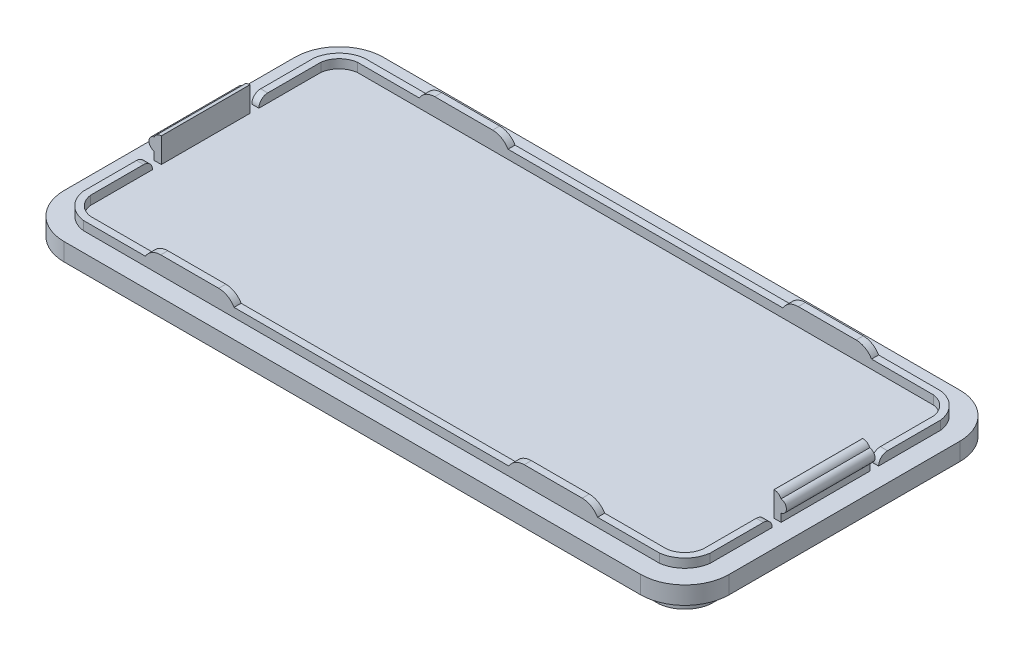
SolidWorks part; units mm, degrees
ref_plane "前视基准面" through (0, 0, 0) normal (0, 0, 1) x (1, 0, 0)
ref_plane "上视基准面" through (0, 0, 0) normal (0, 1, 0) x (1, 0, 0)
ref_plane "右视基准面" through (0, 0, 0) normal (1, 0, 0) x (0, 0, -1)
sketch "zero" plane through (0, 0, 0) normal (0, 1, 0) x (1, 0, 0)
  line L1 (-29.5, 15) -> (29.5, 15)
  line L2 (-32.5, 12) -> (-32.5, -12)
  line L3 (-29.5, -15) -> (29.5, -15)
  line L4 (32.5, 12) -> (32.5, -12)
  line L5 (-32.5, 15) -> (32.5, -15) construction
  line L6 (-32.5, -15) -> (32.5, 15) construction
  line L7 (-25.7, -15) -> (-14.5, -15)
  line L8 (-25.7, -15) -> (-25.7, -9.6569)
  line L9 (-25.7, -9.6569) -> (-14.5, -9.6569)
  line L10 (-14.5, -15) -> (-14.5, -9.6569)
  line L11 (5.2, -15) -> (12.7, -15)
  line L12 (5.2, -15) -> (5.2, -11)
  line L13 (5.2, -11) -> (12.7, -11)
  line L14 (12.7, -15) -> (12.7, -11)
  line L15 (17.8, -15) -> (25.3, -15)
  line L16 (17.8, -15) -> (17.8, -11)
  line L17 (17.8, -11) -> (25.3, -11)
  line L18 (25.3, -15) -> (25.3, -11)
  line L19 (-32.5, 7.7) -> (-19.5, 7.7)
  line L20 (-32.5, 7.7) -> (-32.5, -4.3)
  line L21 (-32.5, -4.3) -> (-19.5, -4.3)
  line L22 (-19.5, 7.7) -> (-19.5, -4.3)
  line L23 (-25.5, 14) -> (25.5, 14)
  line L24 (-25.5, 14) -> (-25.5, 8.8)
  line L25 (-25.5, 8.8) -> (25.5, 8.8)
  line L26 (25.5, 14) -> (25.5, 8.8)
  line L27 (-19.5, 7.2329) -> (-35.5, 7.2329)
  line L28 (-19.5, 7.2329) -> (-19.5, -3.7671)
  line L29 (-19.5, -3.7671) -> (-35.5, -3.7671)
  line L30 (-35.5, 7.2329) -> (-35.5, -3.7671)
  arc A0 (29.5, -15) -> (32.5, -12) centre (29.5, -12) ccw
  arc A1 (29.5, 15) -> (32.5, 12) centre (29.5, 12) cw
  arc A2 (-32.5, -12) -> (-29.5, -15) centre (-29.5, -12) ccw
  arc A3 (-29.5, 15) -> (-32.5, 12) centre (-29.5, 12) ccw
  circle A4 centre (-29, 11.4) radius 3
  circle A5 centre (-29, -11.5) radius 3
  circle A6 centre (29, 11.4) radius 3
  circle A7 centre (29, -11.5) radius 3
  circle A8 centre (-29, 11.4) radius 1.375
  circle A9 centre (-29, -11.5) radius 1.375
  circle A10 centre (29, -11.5) radius 1.375
  circle A11 centre (29, 11.4) radius 1.375
  point P0 (0, 0)
  dimension "D3" = 3
  dimension "D4" = 6
  dimension "D9" = 2.75
  dimension "D1" = 65
  dimension "D2" = 30
  dimension "D5" = 3.6
  dimension "D6" = 3.5
  dimension "D7" = 3.5
  dimension "D8" = 3.5
  dimension "D10" = 12
  dimension "D11" = 7.3
  dimension "D12" = 13
  dimension "D13" = 11.2
  dimension "D14" = 6.8
  dimension "D15" = 19.7
  dimension "D16" = 7.5
  dimension "D17" = 7.5
  dimension "D18" = 5.1
  dimension "D19" = 4
  dimension "D20" = 5.2
  dimension "D21" = 7
  dimension "D22" = 7
  dimension "D23" = 1
  dimension "D24" = 11
  dimension "D25" = 16
sketch "sugar" plane through (0, 0, 0) normal (0, 1, 0) x (1, 0, 0)
  line L1 (-29.5, 15) -> (29.5, 15)
  line L2 (-32.5, 12) -> (-32.5, -12)
  line L3 (-29.5, -15) -> (29.5, -15)
  line L4 (32.5, 12) -> (32.5, -12)
  line L5 (-32.5, 15) -> (32.5, -15) construction
  line L6 (-32.5, -15) -> (32.5, 15) construction
  line L7 (23.5, -11.5) -> (19.5, -11.5)
  line L8 (23.5, -11.5) -> (23.5, -13.9082)
  line L9 (23.5, -13.9082) -> (19.5, -13.9082)
  line L10 (19.5, -11.5) -> (19.5, -13.9082)
  line L11 (16, -11.0071) -> (8.5, -11.0071)
  line L12 (16, -11.0071) -> (16, -15)
  line L13 (16, -15) -> (8.5, -15)
  line L14 (8.5, -11.0071) -> (8.5, -15)
  line L15 (20.5, -13.9082) -> (22.5, -13.9082)
  line L16 (20.5, -13.9082) -> (20.5, -14.8173)
  line L17 (20.5, -14.8173) -> (22.5, -14.8173)
  line L18 (22.5, -13.9082) -> (22.5, -14.8173)
  arc A0 (29.5, 15) -> (32.5, 12) centre (29.5, 12) cw
  arc A1 (29.5, -15) -> (32.5, -12) centre (29.5, -12) ccw
  arc A2 (-32.5, -12) -> (-29.5, -15) centre (-29.5, -12) ccw
  arc A3 (-29.5, 15) -> (-32.5, 12) centre (-29.5, 12) ccw
  circle A4 centre (-29, 11.4) radius 3
  circle A5 centre (-29, 11.4) radius 1.375
  circle A6 centre (-29, -11.5) radius 3
  circle A7 centre (-29, -11.5) radius 1.375
  circle A8 centre (29, 11.4) radius 3
  circle A9 centre (29, 11.4) radius 1.375
  circle A10 centre (29, -11.5) radius 3
  circle A11 centre (29, -11.5) radius 1.375
  dimension "D3" = 3
  dimension "D1" = 65
  dimension "D2" = 30
  dimension "D4" = 9
  dimension "D5" = 4
  dimension "D6" = 3.5
  dimension "D7" = 7.5
  dimension "D8" = 2
  dimension "D9" = 1
sketch "case" plane through (0, 0, 0) normal (0, 1, 0) x (1, 0, 0)
  line L1 (-34.0422, 18) -> (30.9578, 18)
  line L2 (-39.0422, 13) -> (-39.0422, -13)
  line L3 (-34.0422, -18) -> (30.9578, -18)
  line L4 (35.9578, 13) -> (35.9578, -13)
  line L5 (-39.0422, 18) -> (35.9578, -18) construction
  line L6 (-39.0422, -18) -> (35.9578, 18) construction
  arc A0 (-39.0422, -13) -> (-34.0422, -18) centre (-34.0422, -13) ccw
  arc A1 (30.9578, -18) -> (35.9578, -13) centre (30.9578, -13) ccw
  arc A2 (30.9578, 18) -> (35.9578, 13) centre (30.9578, 13) cw
  arc A3 (-34.0422, 18) -> (-39.0422, 13) centre (-34.0422, 13) ccw
  point P0 (-1.5422, 0)
  point P3 (-1.5422, 0)
  dimension "D3" = 5
  dimension "D1" = 75
  dimension "D2" = 36
extrude "凸台-拉伸2" add sketch "case" along normal blind 2
sketch "草图2" plane through (0, 0, 0) normal (0, 1, 0) x (1, 0, 0)
  line L0 (-39.0422, 13) -> (-39.0422, -13) construction
  line L1 (30.9578, 18) -> (-34.0422, 18) construction
  line L4 (-34.0422, -15.05) -> (30.9578, -15.05)
  line L5 (33.0078, -13) -> (33.0078, 13)
  line L6 (30.9578, 15.05) -> (-34.0422, 15.05)
  line L7 (-36.0922, 13) -> (-36.0922, -13)
  line L12 (33.8078, -13) -> (33.8078, 13)
  line L13 (30.9578, 15.85) -> (-34.0422, 15.85)
  line L14 (-36.8922, 13) -> (-36.8922, -13)
  line L15 (-34.0422, -15.85) -> (30.9578, -15.85)
  arc A4 (30.9578, -15.05) -> (33.0078, -13) centre (30.6303, -12.6725) ccw
  arc A5 (33.0078, 13) -> (30.9578, 15.05) centre (30.6303, 12.6725) ccw
  arc A6 (-34.0422, 15.05) -> (-36.0922, 13) centre (-33.7147, 12.6725) ccw
  arc A7 (-36.0922, -13) -> (-34.0422, -15.05) centre (-33.7147, -12.6725) ccw
  arc A12 (30.9578, -15.85) -> (33.8078, -13) centre (30.535, -12.5772) ccw
  arc A13 (33.8078, 13) -> (30.9578, 15.85) centre (30.535, 12.5772) ccw
  arc A14 (-34.0422, 15.85) -> (-36.8922, 13) centre (-33.6194, 12.5772) ccw
  arc A15 (-36.8922, -13) -> (-34.0422, -15.85) centre (-33.6194, -12.5772) ccw
ref_plane "基准面1" through (0, 2, 0) normal (0, 1, 0) x (1, 0, 0)
sketch "草图3" plane through (0, 2, 0) normal (0, 1, 0) x (1, 0, 0)
  line L4 (-34.0422, -15.05) -> (30.9578, -15.05)
  line L5 (33.0078, -13) -> (33.0078, 13)
  line L6 (30.9578, 15.05) -> (-34.0422, 15.05)
  line L7 (-36.0922, 13) -> (-36.0922, -13)
  line L8 (-34.0422, -15.05) -> (30.9578, -15.05)
  line L9 (33.0078, -13) -> (33.0078, 13)
  line L10 (30.9578, 15.05) -> (-34.0422, 15.05)
  line L11 (-36.0922, 13) -> (-36.0922, -13)
  line L12 (-36.8922, 13) -> (-36.8922, -13)
  line L13 (-34.0422, -15.85) -> (30.9578, -15.85)
  line L14 (33.8078, -13) -> (33.8078, 13)
  line L15 (30.9578, 15.85) -> (-34.0422, 15.85)
  line L16 (-36.8922, 13) -> (-36.8922, -13)
  line L17 (-34.0422, -15.85) -> (30.9578, -15.85)
  line L18 (33.8078, -13) -> (33.8078, 13)
  line L19 (30.9578, 15.85) -> (-34.0422, 15.85)
  arc A4 (30.9578, -15.05) -> (33.0078, -13) centre (30.6303, -12.6725) ccw
  arc A5 (33.0078, 13) -> (30.9578, 15.05) centre (30.6303, 12.6725) ccw
  arc A6 (-34.0422, 15.05) -> (-36.0922, 13) centre (-33.7147, 12.6725) ccw
  arc A7 (-36.0922, -13) -> (-34.0422, -15.05) centre (-33.7147, -12.6725) ccw
  arc A8 (30.9578, -15.05) -> (33.0078, -13) centre (30.6303, -12.6725) ccw
  arc A9 (33.0078, 13) -> (30.9578, 15.05) centre (30.6303, 12.6725) ccw
  arc A10 (-34.0422, 15.05) -> (-36.0922, 13) centre (-33.7147, 12.6725) ccw
  arc A11 (-36.0922, -13) -> (-34.0422, -15.05) centre (-33.7147, -12.6725) ccw
  arc A12 (-36.8922, -13) -> (-34.0422, -15.85) centre (-33.6194, -12.5772) ccw
  arc A13 (30.9578, -15.85) -> (33.8078, -13) centre (30.535, -12.5772) ccw
  arc A14 (33.8078, 13) -> (30.9578, 15.85) centre (30.535, 12.5772) ccw
  arc A15 (-34.0422, 15.85) -> (-36.8922, 13) centre (-33.6194, 12.5772) ccw
  arc A16 (-36.8922, -13) -> (-34.0422, -15.85) centre (-33.6194, -12.5772) ccw
  arc A17 (30.9578, -15.85) -> (33.8078, -13) centre (30.535, -12.5772) ccw
  arc A18 (33.8078, 13) -> (30.9578, 15.85) centre (30.535, 12.5772) ccw
  arc A19 (-34.0422, 15.85) -> (-36.8922, 13) centre (-33.6194, 12.5772) ccw
  dimension "D1" = 0
  dimension "D2" = 0
extrude "凸台-拉伸4" add sketch "草图3" along normal blind 1
ref_plane "基准面3" through (33.8078, 0, 0) normal (1, 0, 0) x (0, 0, -1)
sketch "草图7" plane through (0, 2, 0) normal (0, 1, 0) x (1, 0, 0)
  line L0 (-36.8922, 13) -> (-36.8922, -13) construction
  line L1 (-36.8922, 5) -> (-36.0922, 5)
  line L2 (-36.8922, 5) -> (-36.8922, -5)
  line L3 (-36.8922, -5) -> (-36.0922, -5)
  line L4 (-36.0922, 5) -> (-36.0922, -5)
  line L5 (-36.0922, 13) -> (-36.0922, -13) construction
  point P10 (-36.0922, 0)
  dimension "D1" = 5
  dimension "D2" = 10
extrude "凸台-拉伸8" add sketch "草图7" along normal blind 2.8
ref_plane "基准面5" through (0, 0, 5) normal (0, 0, 1) x (1, 0, 0)
sketch "草图8" plane through (0, 0, 5) normal (0, 0, 1) x (1, 0, 0)
  line L0 (-34.0422, 2) -> (-39.0422, 2) construction
  line L1 (-36.8922, 4.8) -> (-36.8922, 3) construction
  circle A0 centre (-36.7922, 3.6) radius 0.7
  dimension "D1" = 1.4
  dimension "D2" = 1.6
  dimension "D3" = 0.1
extrude "凸台-拉伸9" add sketch "草图8" against normal blind 10
fillet "圆角1" radius 0.85 1 edges at (-36.8922, 4.8, 0)
ref_plane "基准面7" through (-36.8922, 0, 0) normal (-1, 0, 0) x (0, 0, 1)
sketch "草图11" plane through (-36.8922, 0, 0) normal (-1, 0, 0) x (0, 0, 1)
  line L0 (-13, 2) -> (13, 2) construction
  line L1 (5, 3) -> (6, 3)
  line L2 (5, 3) -> (5, 2)
  line L3 (5, 2) -> (6, 2)
  line L4 (6, 3) -> (6, 2)
  line L6 (-5, 3) -> (-6, 3)
  line L7 (-5, 3) -> (-5, 2)
  line L8 (-5, 2) -> (-6, 2)
  line L9 (-6, 3) -> (-6, 2)
  dimension "D1" = 1
  dimension "D2" = 1
extrude "切除-拉伸1" cut sketch "草图11" against normal blind 1.2
fillet "圆角2" radius 1 2 edges at (-36.4922, 3, 6) (-36.4922, 3, -6)
ref_plane "基准面8" through (0, 0, 0) normal (0, -1, 0) x (-1, 0, 0)
sketch "草图13" plane through (0, 3, 0) normal (0, 1, 0) x (1, 0, 0)
  line L0 (33.0078, -13) -> (33.0078, 13) construction
  line L1 (33.0078, 5) -> (33.8078, 5)
  line L2 (33.0078, 5) -> (33.0078, -5)
  line L3 (33.0078, -5) -> (33.8078, -5)
  line L4 (33.8078, 5) -> (33.8078, -5)
  line L5 (33.8078, -13) -> (33.8078, 13) construction
  line L7 (35.9578, -13) -> (35.9578, 13) construction
  point P12 (35.9578, 0)
  point P13 (33.8078, 0)
  dimension "D1" = 10
extrude "凸台-拉伸10" add sketch "草图13" along normal blind 1.8
sketch "草图14" plane through (0, 0, 5) normal (0, 0, 1) x (1, 0, 0)
  line L0 (33.8078, 2) -> (30.9578, 2) construction
  line L1 (33.8078, 4.8) -> (33.8078, 3) construction
  circle A0 centre (33.7078, 3.6) radius 0.7
  dimension "D2" = 1.4
  dimension "D1" = 1.6
  dimension "D3" = 0.1
extrude "凸台-拉伸11" add sketch "草图14" against normal blind 10
fillet "圆角3" radius 0.85 1 edges at (33.8078, 4.8, 0)
sketch "草图15" plane through (0, 3, 0) normal (0, 1, 0) x (1, 0, 0)
  line L0 (33.8078, 5) -> (33.8078, 13) construction
  line L1 (33.0078, 5) -> (33.8078, 5)
  line L2 (33.0078, 5) -> (33.0078, 6)
  line L3 (33.0078, 6) -> (33.8078, 6)
  line L4 (33.8078, 5) -> (33.8078, 6)
  line L5 (33.8078, -13) -> (33.8078, -5) construction
  line L6 (33.0078, -5) -> (33.8078, -5)
  line L7 (33.0078, -5) -> (33.0078, -6)
  line L8 (33.0078, -6) -> (33.8078, -6)
  line L9 (33.8078, -5) -> (33.8078, -6)
  dimension "D1" = 1
  dimension "D2" = 1
extrude "切除-拉伸3" cut sketch "草图15" against normal blind 1
fillet "圆角4" radius 1 2 edges at (33.4078, 3, 6) (33.4078, 3, -6)
sketch "草图16" plane through (0, 2, 0) normal (0, 1, 0) x (1, 0, 0)
  line L4 (-34.0422, -15.05) -> (30.9578, -15.05)
  line L5 (33.0078, -13) -> (33.0078, 13)
  line L6 (30.9578, 15.05) -> (-34.0422, 15.05)
  line L7 (-36.0922, 13) -> (-36.0922, -13)
  line L8 (-34.0422, -15.05) -> (30.9578, -15.05)
  line L9 (33.0078, -13) -> (33.0078, 13)
  line L10 (30.9578, 15.05) -> (-34.0422, 15.05)
  line L11 (-36.0922, 13) -> (-36.0922, -13)
  arc A4 (30.9578, -15.05) -> (33.0078, -13) centre (30.6303, -12.6725) ccw
  arc A5 (33.0078, 13) -> (30.9578, 15.05) centre (30.6303, 12.6725) ccw
  arc A6 (-34.0422, 15.05) -> (-36.0922, 13) centre (-33.7147, 12.6725) ccw
  arc A7 (-36.0922, -13) -> (-34.0422, -15.05) centre (-33.7147, -12.6725) ccw
  arc A8 (30.9578, -15.05) -> (33.0078, -13) centre (30.6303, -12.6725) ccw
  arc A9 (33.0078, 13) -> (30.9578, 15.05) centre (30.6303, 12.6725) ccw
  arc A10 (-34.0422, 15.05) -> (-36.0922, 13) centre (-33.7147, 12.6725) ccw
  arc A11 (-36.0922, -13) -> (-34.0422, -15.05) centre (-33.7147, -12.6725) ccw
  dimension "D1" = 0
extrude "凸台-拉伸12" add sketch "草图2" against normal blind 2
sketch "草图18" plane through (0, 0, 0) normal (0, -1, 0) x (1, 0, 0)
  line L2 (-34.0422, 18) -> (30.9578, 18) construction
  line L3 (-39.0422, -13) -> (-39.0422, 13) construction
  circle A0 centre (-37.3172, 15.9) radius 3.225
  circle A1 centre (-37.3172, 15.9) radius 2.225
  circle A2 centre (-29.3672, 15.9) radius 2.225
  circle A3 centre (-29.3672, 15.9) radius 3.225
  circle A4 centre (-21.4172, 15.9) radius 2.225
  circle A5 centre (-21.4172, 15.9) radius 3.225
  circle A6 centre (-13.4672, 15.9) radius 2.225
  circle A7 centre (-13.4672, 15.9) radius 3.225
  circle A8 centre (-5.5172, 15.9) radius 2.225
  circle A9 centre (-5.5172, 15.9) radius 3.225
  circle A10 centre (2.4328, 15.9) radius 2.225
  circle A11 centre (2.4328, 15.9) radius 3.225
  circle A12 centre (10.3828, 15.9) radius 2.225
  circle A13 centre (10.3828, 15.9) radius 3.225
  circle A14 centre (18.3328, 15.9) radius 2.225
  circle A15 centre (18.3328, 15.9) radius 3.225
  circle A16 centre (26.2828, 15.9) radius 2.225
  circle A17 centre (26.2828, 15.9) radius 3.225
  circle A18 centre (34.2328, 15.9) radius 2.225
  circle A19 centre (34.2328, 15.9) radius 3.225
  circle A20 centre (-29.3672, 7.95) radius 2.225
  circle A21 centre (-29.3672, 7.95) radius 3.225
  circle A22 centre (-21.4172, 7.95) radius 2.225
  circle A23 centre (-21.4172, 7.95) radius 3.225
  circle A24 centre (-13.4672, 7.95) radius 2.225
  circle A25 centre (-13.4672, 7.95) radius 3.225
  circle A26 centre (-5.5172, 7.95) radius 2.225
  circle A27 centre (-5.5172, 7.95) radius 3.225
  circle A28 centre (2.4328, 7.95) radius 2.225
  circle A29 centre (2.4328, 7.95) radius 3.225
  circle A30 centre (10.3828, 7.95) radius 2.225
  circle A31 centre (10.3828, 7.95) radius 3.225
  circle A32 centre (18.3328, 7.95) radius 2.225
  circle A33 centre (18.3328, 7.95) radius 3.225
  circle A34 centre (26.2828, 7.95) radius 2.225
  circle A35 centre (26.2828, 7.95) radius 3.225
  circle A36 centre (34.2328, 7.95) radius 2.225
  circle A37 centre (34.2328, 7.95) radius 3.225
  circle A38 centre (-29.3672, 0) radius 2.225
  circle A39 centre (-29.3672, 0) radius 3.225
  circle A40 centre (-21.4172, 0) radius 2.225
  circle A41 centre (-21.4172, 0) radius 3.225
  circle A42 centre (-13.4672, 0) radius 2.225
  circle A43 centre (-13.4672, 0) radius 3.225
  circle A44 centre (-5.5172, 0) radius 2.225
  circle A45 centre (-5.5172, 0) radius 3.225
  circle A46 centre (2.4328, 0) radius 2.225
  circle A47 centre (2.4328, 0) radius 3.225
  circle A48 centre (10.3828, 0) radius 2.225
  circle A49 centre (10.3828, 0) radius 3.225
  circle A50 centre (18.3328, 0) radius 2.225
  circle A51 centre (18.3328, 0) radius 3.225
  circle A52 centre (26.2828, 0) radius 2.225
  circle A53 centre (26.2828, 0) radius 3.225
  circle A54 centre (34.2328, 0) radius 2.225
  circle A55 centre (34.2328, 0) radius 3.225
  circle A56 centre (-29.3672, -7.95) radius 2.225
  circle A57 centre (-29.3672, -7.95) radius 3.225
  circle A58 centre (-21.4172, -7.95) radius 2.225
  circle A59 centre (-21.4172, -7.95) radius 3.225
  circle A60 centre (-13.4672, -7.95) radius 2.225
  circle A61 centre (-13.4672, -7.95) radius 3.225
  circle A62 centre (-5.5172, -7.95) radius 2.225
  circle A63 centre (-5.5172, -7.95) radius 3.225
  circle A64 centre (2.4328, -7.95) radius 2.225
  circle A65 centre (2.4328, -7.95) radius 3.225
  circle A66 centre (10.3828, -7.95) radius 2.225
  circle A67 centre (10.3828, -7.95) radius 3.225
  circle A68 centre (18.3328, -7.95) radius 2.225
  circle A69 centre (18.3328, -7.95) radius 3.225
  circle A70 centre (26.2828, -7.95) radius 2.225
  circle A71 centre (26.2828, -7.95) radius 3.225
  circle A72 centre (34.2328, -7.95) radius 2.225
  circle A73 centre (34.2328, -7.95) radius 3.225
  circle A74 centre (-29.3672, -15.9) radius 2.225
  circle A75 centre (-29.3672, -15.9) radius 3.225
  circle A76 centre (-21.4172, -15.9) radius 2.225
  circle A77 centre (-21.4172, -15.9) radius 3.225
  circle A78 centre (-13.4672, -15.9) radius 2.225
  circle A79 centre (-13.4672, -15.9) radius 3.225
  circle A80 centre (-5.5172, -15.9) radius 2.225
  circle A81 centre (-5.5172, -15.9) radius 3.225
  circle A82 centre (2.4328, -15.9) radius 2.225
  circle A83 centre (2.4328, -15.9) radius 3.225
  circle A84 centre (10.3828, -15.9) radius 2.225
  circle A85 centre (10.3828, -15.9) radius 3.225
  circle A86 centre (18.3328, -15.9) radius 2.225
  circle A87 centre (18.3328, -15.9) radius 3.225
  circle A88 centre (26.2828, -15.9) radius 2.225
  circle A89 centre (26.2828, -15.9) radius 3.225
  circle A90 centre (34.2328, -15.9) radius 2.225
  circle A91 centre (34.2328, -15.9) radius 3.225
  circle A92 centre (-37.3172, 7.95) radius 2.225
  circle A93 centre (-37.3172, 7.95) radius 3.225
  circle A94 centre (-37.3172, 0) radius 2.225
  circle A95 centre (-37.3172, 0) radius 3.225
  circle A96 centre (-37.3172, -7.95) radius 2.225
  circle A97 centre (-37.3172, -7.95) radius 3.225
  circle A98 centre (-37.3172, -15.9) radius 2.225
  circle A99 centre (-37.3172, -15.9) radius 3.225
  dimension "D1" = 6.45
  dimension "D2" = 4.45
  dimension "D3" = 2.1
  dimension "D4" = 1.725
  dimension "D5" = 10
  dimension "D6" = 5
extrude "凸台-拉伸13" add sketch "草图18" along normal blind 2
sketch "草图20" plane through (0, 0, 0) normal (0, -1, 0) x (1, 0, 0)
  line L4 (30.9578, 15.85) -> (29.5074, 15.85)
  line L5 (-36.8922, -11.1469) -> (-36.8922, -12.7031)
  line L6 (-34.0422, -15.85) -> (-32.5918, -15.85)
  line L7 (-36.8922, -11.1469) -> (-36.8922, -12.7031)
  line L8 (30.9578, 15.85) -> (29.5074, 15.85)
  line L10 (-34.0422, -15.85) -> (-32.5918, -15.85)
  line L12 (-36.0922, 13) -> (-36.0922, -13)
  line L13 (-34.0422, -15.05) -> (30.9578, -15.05)
  line L14 (33.0078, -13) -> (33.0078, 13)
  line L15 (30.9578, 15.05) -> (-34.0422, 15.05)
  line L16 (-36.0922, 13) -> (-36.0922, -13)
  line L17 (-34.0422, -15.05) -> (30.9578, -15.05)
  line L18 (33.0078, -13) -> (33.0078, 13)
  line L19 (30.9578, 15.05) -> (-34.0422, 15.05)
  line L34 (-26.1426, -15.85) -> (-24.6418, -15.85)
  line L35 (-26.1426, -15.85) -> (-24.6418, -15.85)
  line L36 (-18.1926, -15.85) -> (-16.6918, -15.85)
  line L37 (-18.1926, -15.85) -> (-16.6918, -15.85)
  line L38 (-10.2426, -15.85) -> (-8.7418, -15.85)
  line L39 (-10.2426, -15.85) -> (-8.7418, -15.85)
  line L40 (-2.2926, -15.85) -> (-0.7918, -15.85)
  line L41 (-2.2926, -15.85) -> (-0.7918, -15.85)
  line L42 (5.6574, -15.85) -> (7.1582, -15.85)
  line L43 (5.6574, -15.85) -> (7.1582, -15.85)
  line L44 (13.6074, -15.85) -> (15.1082, -15.85)
  line L45 (13.6074, -15.85) -> (15.1082, -15.85)
  line L46 (21.5574, -15.85) -> (23.0582, -15.85)
  line L47 (21.5574, -15.85) -> (23.0582, -15.85)
  line L48 (29.5074, -15.85) -> (30.9578, -15.85)
  line L49 (29.5074, -15.85) -> (30.9578, -15.85)
  line L50 (33.8078, -12.7031) -> (33.8078, -11.1469)
  line L51 (33.8078, -12.7031) -> (33.8078, -11.1469)
  line L52 (33.8078, -4.7531) -> (33.8078, -3.1969)
  line L53 (33.8078, -4.7531) -> (33.8078, -3.1969)
  line L54 (33.8078, 3.1969) -> (33.8078, 4.7531)
  line L55 (33.8078, 3.1969) -> (33.8078, 4.7531)
  line L56 (33.8078, 11.1469) -> (33.8078, 12.7031)
  line L57 (33.8078, 11.1469) -> (33.8078, 12.7031)
  line L58 (23.0582, 15.85) -> (21.5574, 15.85)
  line L59 (23.0582, 15.85) -> (21.5574, 15.85)
  line L60 (15.1082, 15.85) -> (13.6074, 15.85)
  line L61 (15.1082, 15.85) -> (13.6074, 15.85)
  line L62 (7.1582, 15.85) -> (5.6574, 15.85)
  line L63 (7.1582, 15.85) -> (5.6574, 15.85)
  line L64 (-0.7918, 15.85) -> (-2.2926, 15.85)
  line L65 (-0.7918, 15.85) -> (-2.2926, 15.85)
  line L66 (-8.7418, 15.85) -> (-10.2426, 15.85)
  line L67 (-8.7418, 15.85) -> (-10.2426, 15.85)
  line L68 (-16.6918, 15.85) -> (-18.1926, 15.85)
  line L69 (-16.6918, 15.85) -> (-18.1926, 15.85)
  line L70 (-24.6418, 15.85) -> (-26.1426, 15.85)
  line L71 (-24.6418, 15.85) -> (-26.1426, 15.85)
  line L72 (-32.5918, 15.85) -> (-34.0422, 15.85)
  line L73 (-32.5918, 15.85) -> (-34.0422, 15.85)
  line L74 (-36.8922, 12.7031) -> (-36.8922, 11.1469)
  line L75 (-36.8922, 12.7031) -> (-36.8922, 11.1469)
  line L76 (-36.8922, 4.7531) -> (-36.8922, 3.1969)
  line L77 (-36.8922, 4.7531) -> (-36.8922, 3.1969)
  line L78 (-36.8922, -3.1969) -> (-36.8922, -4.7531)
  line L79 (-36.8922, -3.1969) -> (-36.8922, -4.7531)
  arc A4 (31.0083, 15.8431) -> (30.9578, 15.85) centre (30.535, 12.5772) ccw
  arc A5 (-34.0422, 15.85) -> (-34.0927, 15.8431) centre (-33.6194, 12.5772) ccw
  arc A6 (-34.0927, -15.8431) -> (-34.0422, -15.85) centre (-33.6194, -12.5772) ccw
  arc A7 (30.9578, -15.85) -> (31.0083, -15.8431) centre (30.535, -12.5772) ccw
  arc A8 (31.0083, 15.8431) -> (30.9578, 15.85) centre (30.535, 12.5772) ccw
  arc A9 (-34.0422, 15.85) -> (-34.0927, 15.8431) centre (-33.6194, 12.5772) ccw
  arc A10 (-34.0927, -15.8431) -> (-34.0422, -15.85) centre (-33.6194, -12.5772) ccw
  arc A11 (30.9578, -15.85) -> (31.0083, -15.8431) centre (30.535, -12.5772) ccw
  arc A12 (-36.0922, -13) -> (-34.0422, -15.05) centre (-33.7147, -12.6725) ccw
  arc A13 (30.9578, -15.05) -> (33.0078, -13) centre (30.6303, -12.6725) ccw
  arc A14 (33.0078, 13) -> (30.9578, 15.05) centre (30.6303, 12.6725) ccw
  arc A15 (-34.0422, 15.05) -> (-36.0922, 13) centre (-33.7147, 12.6725) ccw
  arc A16 (-36.0922, -13) -> (-34.0422, -15.05) centre (-33.7147, -12.6725) ccw
  arc A17 (30.9578, -15.05) -> (33.0078, -13) centre (30.6303, -12.6725) ccw
  arc A18 (33.0078, 13) -> (30.9578, 15.05) centre (30.6303, 12.6725) ccw
  arc A19 (-34.0422, 15.05) -> (-36.0922, 13) centre (-33.7147, 12.6725) ccw
  arc A38 (-36.8922, -12.7031) -> (-34.0927, -15.8431) centre (-37.3172, -15.9) ccw
  arc A39 (-36.8922, -12.7031) -> (-34.0927, -15.8431) centre (-37.3172, -15.9) ccw
  arc A40 (-32.5918, -15.85) -> (-26.1426, -15.85) centre (-29.3672, -15.9) ccw
  arc A41 (-32.5918, -15.85) -> (-26.1426, -15.85) centre (-29.3672, -15.9) ccw
  arc A42 (-24.6418, -15.85) -> (-18.1926, -15.85) centre (-21.4172, -15.9) ccw
  arc A43 (-24.6418, -15.85) -> (-18.1926, -15.85) centre (-21.4172, -15.9) ccw
  arc A44 (-16.6918, -15.85) -> (-10.2426, -15.85) centre (-13.4672, -15.9) ccw
  arc A45 (-16.6918, -15.85) -> (-10.2426, -15.85) centre (-13.4672, -15.9) ccw
  arc A46 (-8.7418, -15.85) -> (-2.2926, -15.85) centre (-5.5172, -15.9) ccw
  arc A47 (-8.7418, -15.85) -> (-2.2926, -15.85) centre (-5.5172, -15.9) ccw
  arc A48 (-0.7918, -15.85) -> (5.6574, -15.85) centre (2.4328, -15.9) ccw
  arc A49 (-0.7918, -15.85) -> (5.6574, -15.85) centre (2.4328, -15.9) ccw
  arc A50 (7.1582, -15.85) -> (13.6074, -15.85) centre (10.3828, -15.9) ccw
  arc A51 (7.1582, -15.85) -> (13.6074, -15.85) centre (10.3828, -15.9) ccw
  arc A52 (15.1082, -15.85) -> (21.5574, -15.85) centre (18.3328, -15.9) ccw
  arc A53 (15.1082, -15.85) -> (21.5574, -15.85) centre (18.3328, -15.9) ccw
  arc A54 (23.0582, -15.85) -> (29.5074, -15.85) centre (26.2828, -15.9) ccw
  arc A55 (23.0582, -15.85) -> (29.5074, -15.85) centre (26.2828, -15.9) ccw
  arc A56 (31.0083, -15.8431) -> (33.8078, -12.7031) centre (34.2328, -15.9) ccw
  arc A57 (31.0083, -15.8431) -> (33.8078, -12.7031) centre (34.2328, -15.9) ccw
  arc A58 (33.8078, -11.1469) -> (33.8078, -4.7531) centre (34.2328, -7.95) ccw
  arc A59 (33.8078, -11.1469) -> (33.8078, -4.7531) centre (34.2328, -7.95) ccw
  arc A60 (33.8078, -3.1969) -> (33.8078, 3.1969) centre (34.2328, 0) ccw
  arc A61 (33.8078, -3.1969) -> (33.8078, 3.1969) centre (34.2328, 0) ccw
  arc A62 (33.8078, 4.7531) -> (33.8078, 11.1469) centre (34.2328, 7.95) ccw
  arc A63 (33.8078, 4.7531) -> (33.8078, 11.1469) centre (34.2328, 7.95) ccw
  arc A64 (33.8078, 12.7031) -> (31.0083, 15.8431) centre (34.2328, 15.9) ccw
  arc A65 (33.8078, 12.7031) -> (31.0083, 15.8431) centre (34.2328, 15.9) ccw
  arc A66 (29.5074, 15.85) -> (23.0582, 15.85) centre (26.2828, 15.9) ccw
  arc A67 (29.5074, 15.85) -> (23.0582, 15.85) centre (26.2828, 15.9) ccw
  arc A68 (21.5574, 15.85) -> (15.1082, 15.85) centre (18.3328, 15.9) ccw
  arc A69 (21.5574, 15.85) -> (15.1082, 15.85) centre (18.3328, 15.9) ccw
  arc A70 (13.6074, 15.85) -> (7.1582, 15.85) centre (10.3828, 15.9) ccw
  arc A71 (13.6074, 15.85) -> (7.1582, 15.85) centre (10.3828, 15.9) ccw
  arc A72 (5.6574, 15.85) -> (-0.7918, 15.85) centre (2.4328, 15.9) ccw
  arc A73 (5.6574, 15.85) -> (-0.7918, 15.85) centre (2.4328, 15.9) ccw
  arc A74 (-2.2926, 15.85) -> (-8.7418, 15.85) centre (-5.5172, 15.9) ccw
  arc A75 (-2.2926, 15.85) -> (-8.7418, 15.85) centre (-5.5172, 15.9) ccw
  arc A76 (-10.2426, 15.85) -> (-16.6918, 15.85) centre (-13.4672, 15.9) ccw
  arc A77 (-10.2426, 15.85) -> (-16.6918, 15.85) centre (-13.4672, 15.9) ccw
  arc A78 (-18.1926, 15.85) -> (-24.6418, 15.85) centre (-21.4172, 15.9) ccw
  arc A79 (-18.1926, 15.85) -> (-24.6418, 15.85) centre (-21.4172, 15.9) ccw
  arc A80 (-26.1426, 15.85) -> (-32.5918, 15.85) centre (-29.3672, 15.9) ccw
  arc A81 (-26.1426, 15.85) -> (-32.5918, 15.85) centre (-29.3672, 15.9) ccw
  arc A82 (-34.0927, 15.8431) -> (-36.8922, 12.7031) centre (-37.3172, 15.9) ccw
  arc A83 (-34.0927, 15.8431) -> (-36.8922, 12.7031) centre (-37.3172, 15.9) ccw
  arc A84 (-36.8922, 11.1469) -> (-36.8922, 4.7531) centre (-37.3172, 7.95) ccw
  arc A85 (-36.8922, 11.1469) -> (-36.8922, 4.7531) centre (-37.3172, 7.95) ccw
  arc A86 (-36.8922, 3.1969) -> (-36.8922, -3.1969) centre (-37.3172, 0) ccw
  arc A87 (-36.8922, 3.1969) -> (-36.8922, -3.1969) centre (-37.3172, 0) ccw
  arc A88 (-36.8922, -4.7531) -> (-36.8922, -11.1469) centre (-37.3172, -7.95) ccw
  arc A89 (-36.8922, -4.7531) -> (-36.8922, -11.1469) centre (-37.3172, -7.95) ccw
  dimension "D1" = 0
  dimension "D2" = 0
extrude "切除-拉伸4" cut sketch "草图20" along normal blind 2
sketch "草图21" plane through (0, 0, 0) normal (0, -1, 0) x (1, 0, 0)
  line L4 (30.9578, 15.05) -> (-34.0422, 15.05)
  line L5 (33.0078, -13) -> (33.0078, 13)
  line L6 (-34.0422, -15.05) -> (30.9578, -15.05)
  line L7 (-36.0922, 13) -> (-36.0922, -13)
  line L8 (30.9578, 15.05) -> (-34.0422, 15.05)
  line L9 (33.0078, -13) -> (33.0078, 13)
  line L10 (-34.0422, -15.05) -> (30.9578, -15.05)
  line L11 (-36.0922, 13) -> (-36.0922, -13)
  line L12 (-36.8922, 13) -> (-36.8922, -13)
  line L13 (30.9578, 15.85) -> (-34.0422, 15.85)
  line L14 (33.8078, -13) -> (33.8078, 13)
  line L15 (-34.0422, -15.85) -> (30.9578, -15.85)
  line L16 (-36.8922, 13) -> (-36.8922, -13)
  line L17 (30.9578, 15.85) -> (-34.0422, 15.85)
  line L18 (33.8078, -13) -> (33.8078, 13)
  line L19 (-34.0422, -15.85) -> (30.9578, -15.85)
  arc A4 (33.0078, 13) -> (30.9578, 15.05) centre (30.6303, 12.6725) ccw
  arc A5 (30.9578, -15.05) -> (33.0078, -13) centre (30.6303, -12.6725) ccw
  arc A6 (-36.0922, -13) -> (-34.0422, -15.05) centre (-33.7147, -12.6725) ccw
  arc A7 (-34.0422, 15.05) -> (-36.0922, 13) centre (-33.7147, 12.6725) ccw
  arc A8 (33.0078, 13) -> (30.9578, 15.05) centre (30.6303, 12.6725) ccw
  arc A9 (30.9578, -15.05) -> (33.0078, -13) centre (30.6303, -12.6725) ccw
  arc A10 (-36.0922, -13) -> (-34.0422, -15.05) centre (-33.7147, -12.6725) ccw
  arc A11 (-34.0422, 15.05) -> (-36.0922, 13) centre (-33.7147, 12.6725) ccw
  arc A12 (-34.0422, 15.85) -> (-36.8922, 13) centre (-33.6194, 12.5772) ccw
  arc A13 (33.8078, 13) -> (30.9578, 15.85) centre (30.535, 12.5772) ccw
  arc A14 (30.9578, -15.85) -> (33.8078, -13) centre (30.535, -12.5772) ccw
  arc A15 (-36.8922, -13) -> (-34.0422, -15.85) centre (-33.6194, -12.5772) ccw
  arc A16 (-34.0422, 15.85) -> (-36.8922, 13) centre (-33.6194, 12.5772) ccw
  arc A17 (33.8078, 13) -> (30.9578, 15.85) centre (30.535, 12.5772) ccw
  arc A18 (30.9578, -15.85) -> (33.8078, -13) centre (30.535, -12.5772) ccw
  arc A19 (-36.8922, -13) -> (-34.0422, -15.85) centre (-33.6194, -12.5772) ccw
  dimension "D1" = 0
  dimension "D2" = 0
extrude "凸台-拉伸14" add sketch "草图21" along normal blind 2
sketch "草图22" plane through (0, 3, 0) normal (0, 1, 0) x (1, 0, 0)
  line L0 (30.9578, 15.85) -> (-34.0422, 15.85) construction
  line L1 (-27.0422, 15.85) -> (-17.0422, 15.85)
  line L2 (-27.0422, 15.85) -> (-27.0422, 15.05)
  line L3 (-27.0422, 15.05) -> (-17.0422, 15.05)
  line L4 (-17.0422, 15.85) -> (-17.0422, 15.05)
  line L5 (30.9578, 15.05) -> (-34.0422, 15.05) construction
  line L6 (-34.0422, -15.05) -> (30.9578, -15.05) construction
  line L7 (13.9578, 15.85) -> (23.9578, 15.85)
  line L8 (13.9578, 15.85) -> (13.9578, 15.05)
  line L9 (13.9578, 15.05) -> (23.9578, 15.05)
  line L10 (23.9578, 15.85) -> (23.9578, 15.05)
  line L11 (-27.0422, -15.05) -> (-17.0422, -15.05)
  line L12 (-27.0422, -15.05) -> (-27.0422, -15.85)
  line L13 (-27.0422, -15.85) -> (-17.0422, -15.85)
  line L14 (-17.0422, -15.05) -> (-17.0422, -15.85)
  line L15 (-34.0422, -15.85) -> (30.9578, -15.85) construction
  line L16 (35.9578, -13) -> (35.9578, 13) construction
  line L17 (13.9578, -15.05) -> (23.9578, -15.05)
  line L18 (13.9578, -15.05) -> (13.9578, -15.85)
  line L19 (13.9578, -15.85) -> (23.9578, -15.85)
  line L20 (23.9578, -15.05) -> (23.9578, -15.85)
  line L21 (-39.0422, 13) -> (-39.0422, -13) construction
  dimension "D1" = 10
  dimension "D2" = 10
  dimension "D3" = 10
  dimension "D4" = 10
  dimension "D5" = 12
  dimension "D6" = 12
  dimension "D7" = 12
  dimension "D8" = 12
extrude "凸台-拉伸16" add sketch "草图22" along normal blind 1
fillet "圆角5" radius 2 8 edges at (-27.0422, 4, 15.45) (-17.0422, 4, 15.45) (23.9578, 4, 15.45) (13.9578, 4, 15.45) (23.9578, 4, -15.45) (13.9578, 4, -15.45) (-17.0422, 4, -15.45) (-27.0422, 4, -15.45)
